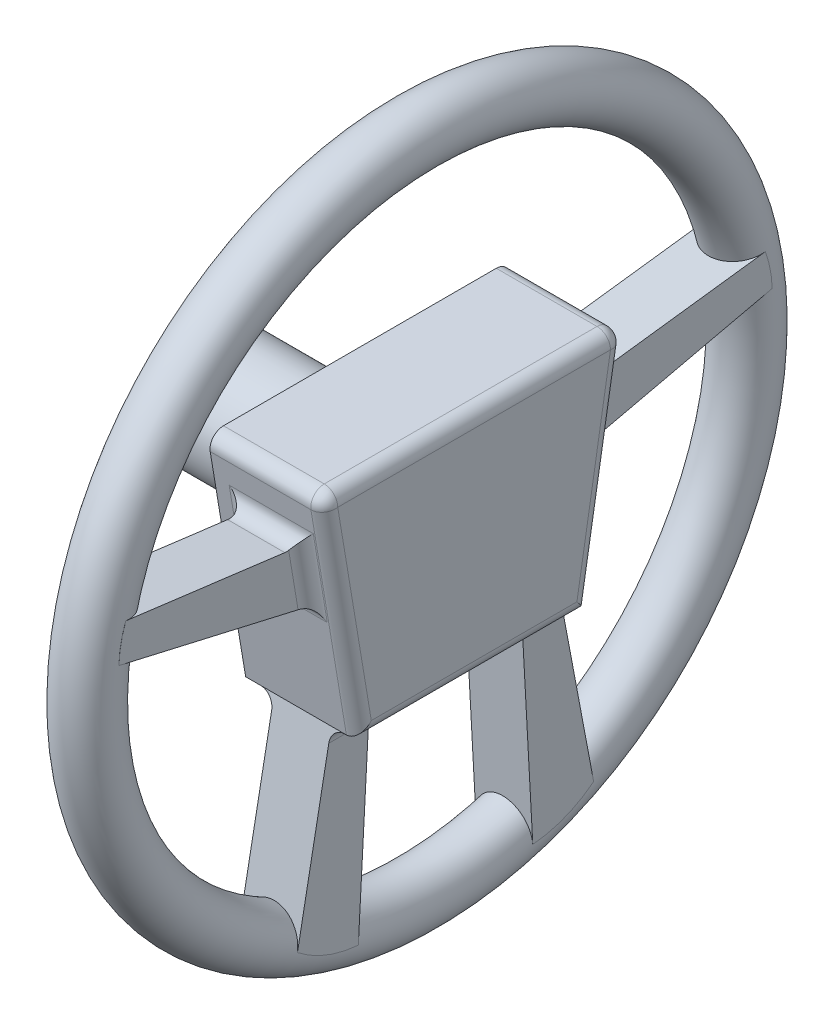
SolidWorks part; units mm, degrees
ref_plane "Front Plane" through (0, 0, 0) normal (0, 0, 1) x (1, 0, 0)
ref_plane "Top Plane" through (0, 0, 0) normal (0, 1, 0) x (1, 0, 0)
ref_plane "Right Plane" through (0, 0, 0) normal (1, 0, 0) x (0, 0, -1)
sketch "Sketch1" plane through (0, 0, 0) normal (1, 0, 0) x (0, 0, -1)
  circle A0 centre (0, 0) radius 38.1
  dimension "D1" = 76.2
extrude "Boss-Extrude1" add sketch "Sketch1" along normal blind 101.6
sketch "Sketch2" plane through (101.6, 0, 0) normal (1, 0, 0) x (0, 0, -1)
  line L0 (0, 0) -> (0, 76.2) construction
  line L1 (0, 0) -> (0, -76.2) construction
  line L2 (0, 0) -> (228.6, 0) construction
  line L3 (-101.6, 76.2) -> (101.6, 76.2)
  line L4 (-76.2, -76.2) -> (76.2, -76.2)
  line L5 (-101.6, 76.2) -> (-76.2, -76.2)
  line L6 (101.6, 76.2) -> (76.2, -76.2)
  point P8 (0, 76.2)
  point P11 (0, -76.2)
  dimension "D1" = 76.2
  dimension "D2" = 76.2
  dimension "D3" = 228.6
  dimension "D4" = 203.2
  dimension "D5" = 152.4
extrude "Boss-Extrude2" add sketch "Sketch2" along normal blind 76.2
chamfer "Chamfer1" distance 20 angle 45 1 edges at (101.6, 0, -38.1)
ref_plane "Plane1" through (139.7, 0, 0) normal (1, 0, 0) x (0, 0, -1)
sketch "Sketch3" plane through (139.7, 0, 0) normal (1, 0, 0) x (0, 0, -1)
  circle A0 centre (0, 0) radius 220
  dimension "D1" = 440
sketch "Sketch4" plane through (0, 0, 0) normal (0, 0, 1) x (1, 0, 0)
  line L0 (139.7, -220) -> (139.7, 220) construction
  circle A0 centre (139.7, 220) radius 19.05
  dimension "D1" = 38.1
  dimension "D2" = 220
sweep "Sweep1" add profiles "Sketch4" path "Sketch3"
sketch "Sketch5" plane through (139.7, 0, 0) normal (1, 0, 0) x (0, 0, -1)
  line L0 (-95.25, 38.1) -> (-194.4229, 50.8)
  line L1 (-101.6, 76.2) -> (-76.2, -76.2) construction
  line L2 (-88.9, 0) -> (-199.3383, 25.4)
  line L3 (-95.25, 38.1) -> (-88.9, 0)
  line L4 (101.6, 76.2) -> (-101.6, 76.2) construction
  line L5 (-76.2, -76.2) -> (-95.25, -176.9416)
  line L6 (-76.2, -76.2) -> (-50.8, -76.2)
  line L7 (-76.2, -76.2) -> (76.2, -76.2) construction
  line L8 (-50.8, -76.2) -> (-57.15, -192.652)
  line L9 (0, 76.2) -> (0, -76.2) construction
  line L16 (-194.4229, 50.8) -> (-213.3186, 53.2198)
  line L17 (-199.3383, 25.4) -> (-217.9036, 29.6699)
  line L18 (-95.25, -176.9416) -> (-98.7896, -195.6599)
  line L19 (-57.15, -192.652) -> (-58.1872, -211.6737)
  line L20 (57.15, -192.652) -> (58.1872, -211.6737)
  line L21 (95.25, -176.9416) -> (98.7896, -195.6599)
  line L22 (199.3383, 25.4) -> (217.9036, 29.6699)
  line L23 (194.4229, 50.8) -> (213.3186, 53.2198)
  line L24 (50.8, -76.2) -> (57.15, -192.652)
  line L25 (76.2, -76.2) -> (50.8, -76.2)
  line L26 (76.2, -76.2) -> (95.25, -176.9416)
  line L27 (95.25, 38.1) -> (88.9, 0)
  line L28 (88.9, 0) -> (199.3383, 25.4)
  line L29 (95.25, 38.1) -> (194.4229, 50.8)
  circle A0 centre (0, 0) radius 200.95 construction
  arc A5 (-217.9036, 29.6699) -> (-213.3186, 53.2198) centre (-142.9411, 27.2966) cw
  arc A6 (-98.7896, -195.6599) -> (-58.1872, -211.6737) centre (-52.1616, -136.9162) ccw
  arc A7 (98.7896, -195.6599) -> (58.1872, -211.6737) centre (52.1616, -136.9162) cw
  arc A8 (217.9036, 29.6699) -> (213.3186, 53.2198) centre (142.9411, 27.2966) ccw
  dimension "D9" = 75
  dimension "D1" = 38.1
  dimension "D2" = 25.4
  dimension "D3" = 25.4
  dimension "D4" = 38.1
  dimension "D5" = 25.4
  dimension "D6" = 38.1
  dimension "D7" = 19.05
  dimension "D8" = 19.05
extrude "Boss-Extrude3" add sketch "Sketch5" along normal blind 19.05 and the other way blind 19.05
fillet "Fillet1" radius 9 20 edges at (177.8, -76.2, 0) (177.8, 0, 88.9) (177.8, 76.2, 0) (177.8, 0, -88.9) (139.7, 76.2, 101.6) (139.7, 76.2, -101.6) (139.7, 38.1, -95.25) (120.65, 19.05, -92.075) (139.7, 0, -88.9) (158.75, 19.05, -92.075) (158.75, -76.2, -63.5) (139.7, -76.2, -50.8) (120.65, -76.2, -63.5) (120.65, -76.2, 63.5) (139.7, -76.2, 50.8) (158.75, -76.2, 63.5) (120.65, 19.05, 92.075) (139.7, 38.1, 95.25) (139.7, 0, 88.9) (158.75, 19.05, 92.075)
